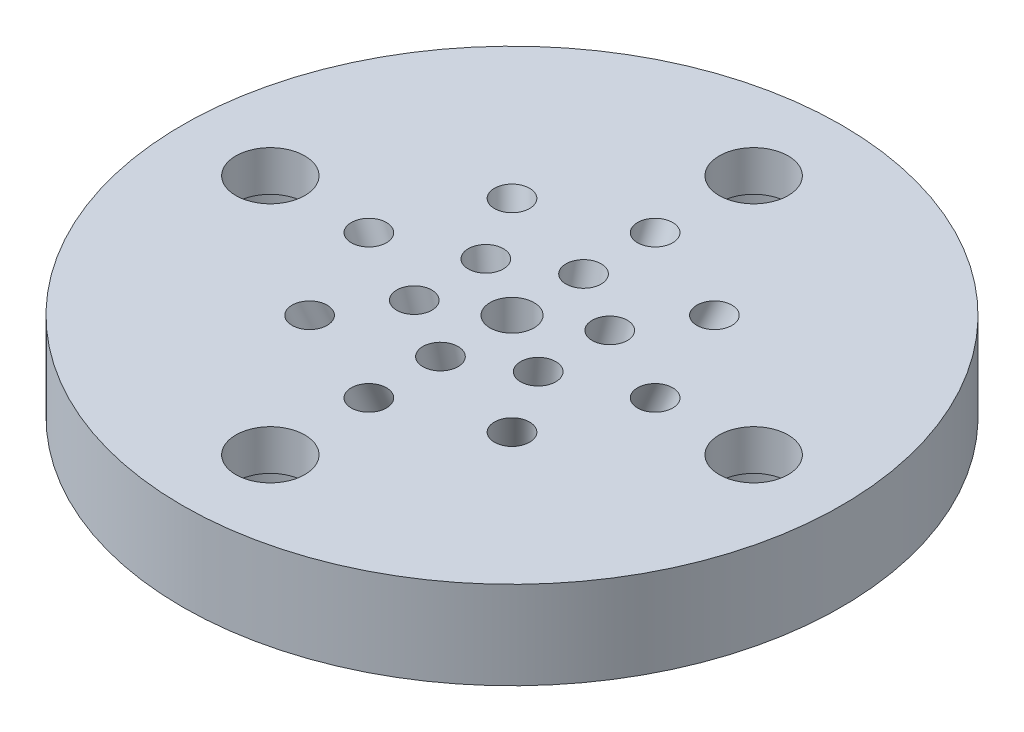
SolidWorks part; units mm, degrees
note: '?' marks a value the reader was unsure of.
ref_plane "Front Plane" through (0, 0, 0) normal (0, 0, 1) x (1, 0, 0)
ref_plane "Top Plane" through (0, 0, 0) normal (0, 1, 0) x (1, 0, 0)
ref_plane "Right Plane" through (0, 0, 0) normal (1, 0, 0) x (0, 0, -1)
sketch "Sketch1" plane through (0, 0, 0) normal (0, 1, 0) x (1, 0, 0)
  circle A1 centre (0, 0) radius 50.8
  dimension "D1" = 101.6
extrude "Boss-Extrude1" add sketch "Sketch1" along normal blind 25.4
sketch "Sketch2" plane through (0, 0, 0) normal (0, -1, 0) x (1, 0, 0)
  circle A0 centre (0, 0) radius 50.8
  circle A1 centre (0, 0) radius 69.85
  dimension "D1" = 139.7
extrude "Boss-Extrude2" add sketch "Sketch2" against normal blind 12.7
sketch "Sketch3" plane through (0, 0, 0) normal (0, -1, 0) x (1, 0, 0)
  circle A0 centre (0, 0) radius 49.53
  circle A1 centre (0, 0) radius 47.625
  dimension "D1" = 99.06
  dimension "D2" = 95.25
extrude "Cut-Extrude1" cut sketch "Sketch3" against normal blind 1.1176
sketch "Sketch4" plane through (0, 0, 0) normal (0, -1, 0) x (1, 0, 0)
  circle A0 centre (0, -59.9186) radius 3.175
  circle A1 centre (-42.3688, -42.3688) radius 3.175
  circle A2 centre (-59.9186, 0) radius 3.175
  circle A3 centre (-42.3688, 42.3688) radius 3.175
  circle A4 centre (0, 59.9186) radius 3.175
  circle A5 centre (42.3688, 42.3688) radius 3.175
  circle A6 centre (59.9186, 0) radius 3.175
  circle A7 centre (42.3688, -42.3688) radius 3.175
  point P35 (0, 0)
  dimension "D2" = 6.35
  dimension "D1" = 59.9186
  dimension "D3" = 8
extrude "Cut-Extrude2" cut sketch "Sketch4" against normal up to next
sketch "Sketch5" plane through (0, 25.4, 0) normal (0, 1, 0) x (1, 0, 0)
  circle A0 centre (0, 0) radius 11.43
  dimension "D1" = 22.86
extrude "Cut-Extrude3" cut sketch "Sketch5" against normal blind 19.05 from offset 0
sketch "Sketch6" plane through (0, 6.35, 0) normal (0, 1, 0) x (1, 0, 0)
  circle A0 centre (0, 0) radius 1.5875
  dimension "D1" = 3.175
extrude "Cut-Extrude4" cut sketch "Sketch6" against normal up to next
sketch "Sketch30" plane through (0, 0, 0) normal (1, 0, 0) x (0, 0, -1)
  line L0 (0, -28.0613) -> (0, 0) construction
sketch "Sketch42" plane through (0, 0, 0) normal (0, -1, 0) x (1, 0, 0)
  circle A0 centre (0, 0) radius 23.8125
  dimension "D1" = 47.625
extrude "Cut-Extrude9" cut sketch "Sketch42" against normal blind 30.48 flip side to cut
sketch "Sketch43" plane through (0, 25.4, 0) normal (0, 1, 0) x (1, 0, 0)
  circle A0 centre (0, 0) radius 20.6375
extrude "Cut-Extrude10" cut sketch "Sketch43" against normal blind 19.05
hole_wizard "CBORE for #10 Binding Head Machine Screw1" positions "Sketch50" profile "Sketch51" counterbore size "#10" standard "ANSI Inch" end condition through all
sketch "Sketch50" plane through (0, 0, 0) normal (0, -1, 0) x (-1, 0, 0)
  line L0 (0, 0) -> (0, -25.4) construction
  line L2 (0, 0) -> (0, 25.4) construction
  line L4 (0, 0) -> (-25.4, 0) construction
  line L6 (0, 0) -> (25.4, 0) construction
  circle A0 centre (0, 0) radius 17.4625 construction
  point P0 (0, -17.4625)
  point P2 (-17.4625, 0)
  point P4 (17.4625, 0)
  point P6 (0, 17.4625)
  dimension "D1" = 34.925
sketch "Sketch51" plane through (0, 0, 17.4625) normal (1, 0, 0) x (0, 0, -1)
  line L0 (0, 0) -> (0, 25.4)
  line L1 (0, 25.4) -> (2.4892, 25.4)
  line L3 (2.4892, 25.4) -> (2.4892, 3.429)
  line L4 (2.4892, 3.429) -> (4.7625, 3.429)
  line L5 (4.7625, 3.429) -> (4.7625, 0)
  line L7 (4.7625, 0) -> (0, 0)
  line L11 (0, -6.35) -> (0, 107.95) construction
  dimension "Thru Hole Dia." = 4.9784
  dimension "Thru Hole Depth" = 25.4
  dimension "C'Bore Dia." = 9.525
  dimension "C'Bore Depth" = 3.429
sketch "Sketch52" plane through (0, 25.4, 0) normal (0, 1, 0) x (1, 0, 0)
  circle A0 centre (0, 0) radius 23.8125
  dimension "D1" = 47.625
extrude "Cut-Extrude11" cut sketch "Sketch52" against normal blind 19.05
sketch "Sketch54" plane through (0, 0, 0) normal (0, 0, 1) x (1, 0, 0)
  line L0 (0, 0) -> (0, -17.78)
  dimension "D1" = 17.78
sketch "Sketch55" plane through (0, 0, 0) normal (0, -1, 0) x (1, 0, 0)
  circle A0 centre (0, 3.81) radius 1.27
  dimension "D1" = 2.54
  dimension "D2" = 3.81
ref_axis "Axis1" through (0, 0, 3.81) along (0, -0.9778, -0.2095)?
extrude "Cut-Extrude12" cut sketch "Sketch55" along direction (0, -0.9778, -0.2095) on the side against the normal blind 7.62 contours A0
pattern_circular "CirPattern1" count 6 over 360 about axis through (0, 0, 0) along (0, -1, 0) of "Cut-Extrude12" reverse direction yes
sketch "Sketch57" plane through (0, 0, 0) normal (0, -1, 0) x (1, 0, 0)
  circle A0 centre (0, 7.62) radius 1.27
  dimension "D1" = 2.54
  dimension "D2" = 7.62
ref_axis "Axis2" through (0, 0, 7.62) along (0, -0.9191, -0.3939)?
extrude "Cut-Extrude13" cut sketch "Sketch57" along direction (0, -0.9191, -0.3939) on the side against the normal blind 7.62 contours A0
pattern_circular "CirPattern2" count 8 over 360 about axis through (0, 0, 0) along (0, -1, 0) of "Cut-Extrude13" reverse direction yes
